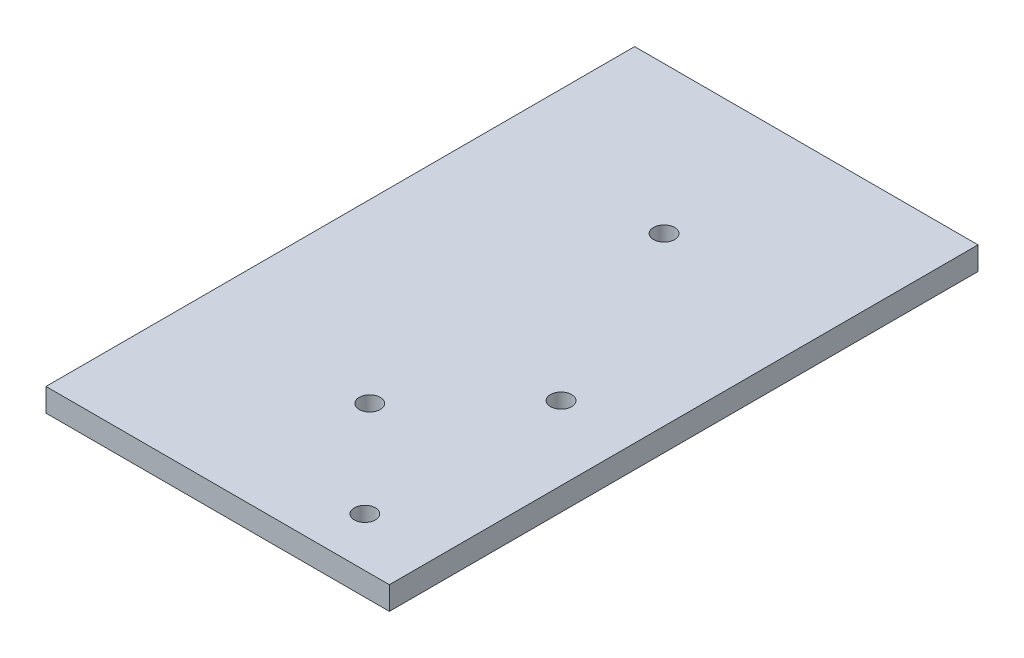
SolidWorks part; units mm, degrees
ref_plane "Front Plane" through (0, 0, 0) normal (0, 0, 1) x (1, 0, 0)
ref_plane "Top Plane" through (0, 0, 0) normal (0, 1, 0) x (1, 0, 0)
ref_plane "Right Plane" through (0, 0, 0) normal (1, 0, 0) x (0, 0, -1)
sketch "Sketch2" plane through (0, 0, 0) normal (0, 1, 0) x (1, 0, 0)
  line L2 (0, 0) -> (0, 152.4)
  line L4 (88.9, 0) -> (88.9, 152.4)
  line L10 (-1000, 76.2) -> (49000, 76.2) construction
  line L13 (0, 152.4) -> (88.9, 152.4)
  line L14 (0, 0) -> (88.9, 0)
  point P11 (0, 76.2)
  dimension "D1" = 152.4
  dimension "D2" = 88.9
extrude "Boss-Extrude1" add sketch "Sketch2" along normal blind 5.9944 contours L4 L13 L2 L14
sketch "Sketch4" plane through (0, 5.9944, 0) normal (0, 1, 0) x (1, 0, 0)
  line L0 (0, 0) -> (0, 152.4) construction
  line L2 (45.72, 114.3) -> (45.72, 38.1) construction
  circle A0 centre (45.72, 114.3) radius 2.7305
  circle A1 centre (45.72, 38.1) radius 2.7305
  point P4 (45.72, 76.2)
  point P12 (0, 76.2)
  dimension "D3" = 5.461
  dimension "D4" = 5.461
  dimension "D1" = 76.2
  dimension "D2" = 45.72
extrude "Cut-Extrude2" cut sketch "Sketch4" against normal through all both
sketch "Sketch5" plane through (0, 5.9944, 0) normal (0, 1, 0) x (1, 0, 0)
  line L0 (88.9, 0) -> (88.9, 152.4) construction
  line L5 (0, 0) -> (88.9, 0) construction
  circle A0 centre (69.85, 63.5) radius 2.7305
  circle A1 centre (69.85, 12.7) radius 2.7305
  dimension "D1" = 5.461
  dimension "D2" = 5.461
  dimension "D3" = 50.8
  dimension "D6" = 19.05
  dimension "D7" = 12.7
extrude "Cut-Extrude3" cut sketch "Sketch5" against normal through all both and the other way through all
sketch "Sketch6" plane through (0, 5.9944, 0) normal (0, 1, 0) x (1, 0, 0)
  line L1 (39.5669, 149.2321) -> (2.8131, 149.2321) construction
  line L2 (39.5669, 149.2321) -> (39.5669, 112.4783) construction
  line L3 (39.5669, 112.4783) -> (2.8131, 112.4783) construction
  line L4 (2.8131, 149.2321) -> (2.8131, 112.4783) construction
  circle A0 centre (39.5669, 112.4783) radius 1.905
  circle A1 centre (2.8131, 112.4783) radius 1.905
  circle A2 centre (2.8131, 149.2321) radius 1.905
  circle A3 centre (39.5669, 149.2321) radius 1.905
  dimension "D3" = 3.81
  dimension "D4" = 3.81
  dimension "D5" = 3.81
  dimension "D6" = 3.81
  dimension "D1" = 36.7538
  dimension "D2" = 36.7538
equation "\"threaded_insert_hole\"=0.1472"
equation "\"th\"=1.25249"
